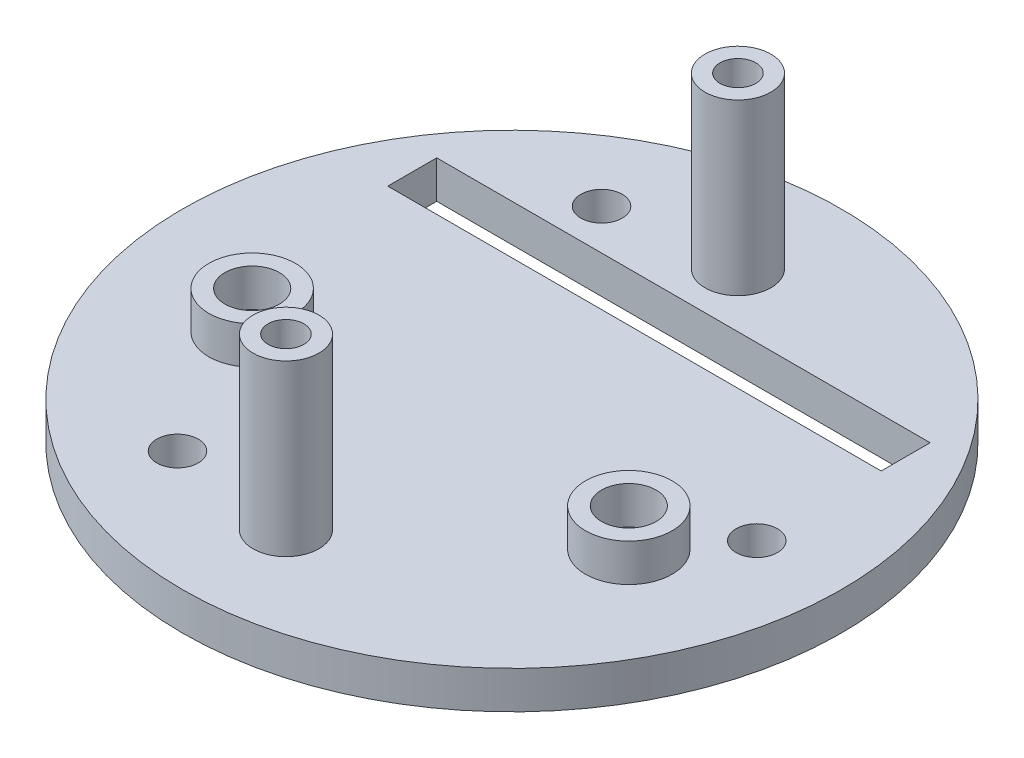
SolidWorks part; units mm, degrees
note: The reader was unsure of these and kept them because the rebuilt part matched: shared geometry of "草图1<4>", "草图1<5>", "草图1<6>".
ref_plane "前视基准面" through (0, 0, 0) normal (0, 0, 1) x (1, 0, 0)
ref_plane "上视基准面" through (0, 0, 0) normal (0, 1, 0) x (1, 0, 0)
ref_plane "右视基准面" through (0, 0, 0) normal (1, 0, 0) x (0, 0, -1)
sketch "草图1" plane through (0, 0, 0) normal (0, 1, 0) x (1, 0, 0)
  line L18 (0, 0) -> (0, 1.6067)
  line L21 (-13.1, 9.1067) -> (-13.1, 6.5067)
  line L24 (-13.1, -5.8933) -> (13.1, -5.8933)
  line L25 (-13.1, -5.8933) -> (-13.1, 9.1067)
  line L26 (-13.1, 9.1067) -> (13.1, 9.1067)
  line L27 (13.1, -5.8933) -> (13.1, 9.1067)
  line L28 (-13.1, -5.8933) -> (13.1, 9.1067) construction
  line L29 (13.1, -5.8933) -> (-13.1, 9.1067) construction
  line L30 (-13.1, 6.5067) -> (13.1, 6.5067)
  line L31 (0, 1.6067) -> (0, -5.0959) construction
  circle A2 centre (-6.5, 11.2583) radius 1.1
  circle A36 centre (0, 0) radius 17.5
  circle A37 centre (13, 0) radius 1.1
  circle A38 centre (-6.5, -11.2583) radius 1.1
  circle A39 centre (-10, -3.7933) radius 1.45
  circle A40 centre (10, -3.7933) radius 1.45
  circle A41 centre (-10, -3.7933) radius 2.3
  circle A43 centre (10, -3.7933) radius 2.3
  circle A44 centre (0, 12) radius 0.95
  circle A45 centre (0.002, 0) radius 17.5
  circle A46 centre (0.002, -12) radius 0.95
  circle A47 centre (0, 12) radius 1.75
  circle A48 centre (0.002, -12) radius 1.75
  circle A49 centre (-6.5, 11.2583) radius 4.5 construction
  point P1 (0, 1.6067)
  point P2 (0, 1.6067)
  point P17 (0, 0)
  point P35 (0.001, 0)
  point P87 (0, 0)
  dimension "D1" = 3
  dimension "D2" = 13
  dimension "D3" = 7.5
  dimension "D5" = 2.1
  dimension "D6" = 2.6
  dimension "D7" = 2
  dimension "D8" = 20
  dimension "D9" = 26.2
extrude "凸台-拉伸1" add sketch "草图1" along normal blind 2 contours A36
extrude "切除-拉伸2" cut sketch "草图1<4>" along normal up to next contours L21 L30 L27 L26 | A38 | A37 | A2
sketch "草图1<4>" plane through (0, 0, 0) normal (0, 1, 0) x (1, 0, 0) same geometry as "草图1"
extrude "凸台-拉伸2" add sketch "草图1<5>" along normal blind 4 contours L24 A41 A39 | L24 A41 | L24 A43 A40 | L24 A43 | A47
sketch "草图1<5>" plane through (0, 0, 0) normal (0, 1, 0) x (1, 0, 0) same geometry as "草图1"
extrude "凸台-拉伸3" add sketch "草图1<6>" along normal blind 11 contours A47 A44 | A48 A46
sketch "草图1<6>" plane through (0, 0, 0) normal (0, 1, 0) x (1, 0, 0) same geometry as "草图1"
